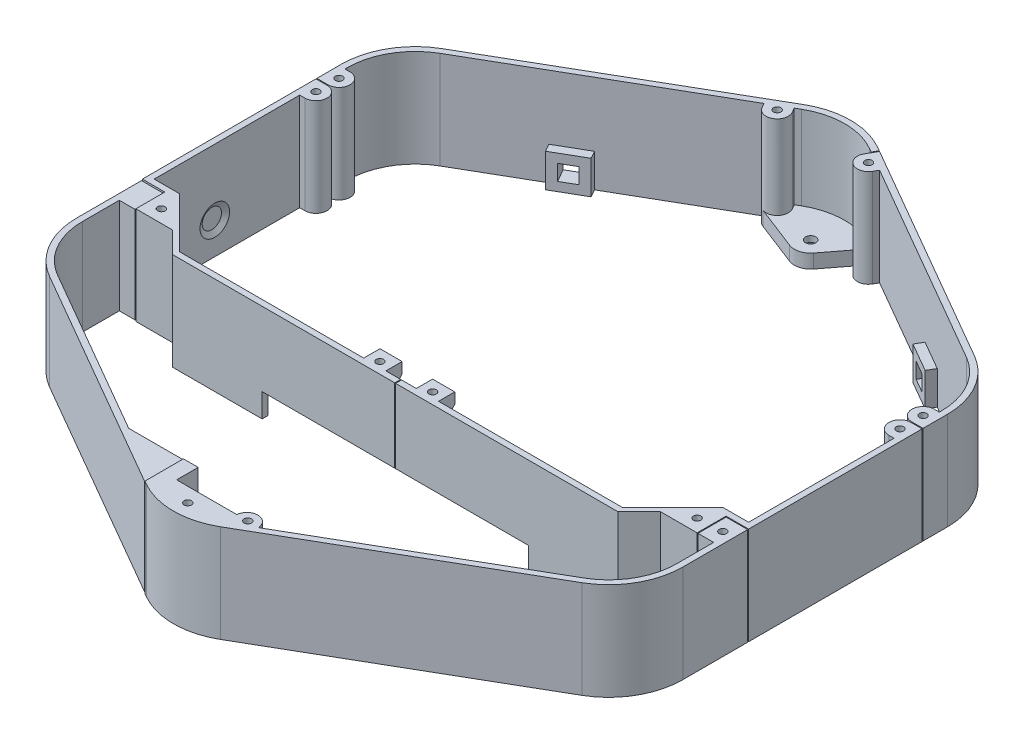
SolidWorks part; units mm, degrees
material "ABS_Perso"
ref_plane "Plan de face" through (0, 0, 0) normal (0, 0, 1) x (1, 0, 0)
ref_plane "Plan de dessus" through (0, 0, 0) normal (0, 1, 0) x (1, 0, 0)
ref_plane "Plan de droite" through (0, 0, 0) normal (1, 0, 0) x (0, 0, -1)
sketch "Esquisse1" plane through (0, 0, 0) normal (0, 1, 0) x (1, 0, 0)
  line L0 (-102.5, 0) -> (102.5, 0) construction
  line L1 (-102.5, 59.1784) -> (-102.5, -59.1784)
  line L2 (102.5, 59.1784) -> (102.5, -59.1784)
  line L3 (-102.5, -59.1784) -> (0, -118.3568)
  line L5 (0, -118.3568) -> (102.5, -59.1784)
  line L6 (102.5, 59.1784) -> (0, 118.3568)
  line L8 (0, 118.3568) -> (-102.5, 59.1784)
  line L9 (0, -118.3568) -> (0, 118.3568) construction
  line L10 (-102.5, 59.1784) -> (102.5, 59.1784) construction
  line L11 (102.5, -59.1784) -> (-102.5, -59.1784) construction
  circle A1 centre (0, 0) radius 102.5 construction
  point P13 (0, 0)
  dimension "D5" = 118.3568
  dimension "D1" = 205
  dimension "D6" = 118.3568
extrude "Boss.-Extru.1" add sketch "Esquisse1" along normal blind 33
fillet "Congé8" radius 25 6 edges at (102.5, 16.5, 59.1784) (-102.5, 16.5, 59.1784) (-102.5, 16.5, -59.1784) (102.5, 16.5, -59.1784) (0, 16.5, -118.3568) (0, 16.5, 118.3568)
sketch "Esquisse22" plane through (0, 33, 0) normal (0, 1, 0) x (1, 0, 0)
  line L0 (89, 64.6632) -> (11.5, 109.4079)
  line L1 (-11.5, 109.4079) -> (-89, 64.6632)
  line L2 (-100.5, 44.7446) -> (-100.5, -44.7446)
  line L3 (-89, -64.6632) -> (-11.5, -109.4079)
  line L4 (11.5, -109.4079) -> (89, -64.6632)
  line L5 (100.5, -44.7446) -> (100.5, 44.7446)
  line L6 (90, 66.3953) -> (12.5, 111.1399)
  line L7 (-12.5, 111.1399) -> (-90, 66.3953)
  line L8 (-102.5, 44.7446) -> (-102.5, -44.7446)
  line L9 (-90, -66.3953) -> (-12.5, -111.1399)
  line L10 (12.5, -111.1399) -> (90, -66.3953)
  line L11 (102.5, -44.7446) -> (102.5, 44.7446)
  line L12 (90, 66.3953) -> (12.5, 111.1399) construction
  line L13 (-12.5, 111.1399) -> (-90, 66.3953) construction
  line L14 (-102.5, 44.7446) -> (-102.5, -44.7446) construction
  line L15 (-90, -66.3953) -> (-12.5, -111.1399) construction
  line L16 (12.5, -111.1399) -> (90, -66.3953) construction
  line L17 (102.5, -44.7446) -> (102.5, 44.7446) construction
  arc A0 (11.5, 109.4079) -> (-11.5, 109.4079) centre (0, 89.4893) ccw
  arc A1 (-89, 64.6632) -> (-100.5, 44.7446) centre (-77.5, 44.7446) ccw
  arc A2 (-100.5, -44.7446) -> (-89, -64.6632) centre (-77.5, -44.7446) ccw
  arc A3 (-11.5, -109.4079) -> (11.5, -109.4079) centre (0, -89.4893) ccw
  arc A4 (89, -64.6632) -> (100.5, -44.7446) centre (77.5, -44.7446) ccw
  arc A5 (100.5, 44.7446) -> (89, 64.6632) centre (77.5, 44.7446) ccw
  arc A6 (12.5, 111.1399) -> (-12.5, 111.1399) centre (0, 89.4893) ccw
  arc A7 (-90, 66.3953) -> (-102.5, 44.7446) centre (-77.5, 44.7446) ccw
  arc A8 (-102.5, -44.7446) -> (-90, -66.3953) centre (-77.5, -44.7446) ccw
  arc A9 (-12.5, -111.1399) -> (12.5, -111.1399) centre (0, -89.4893) ccw
  arc A10 (90, -66.3953) -> (102.5, -44.7446) centre (77.5, -44.7446) ccw
  arc A11 (102.5, 44.7446) -> (90, 66.3953) centre (77.5, 44.7446) ccw
  arc A12 (12.5, 111.1399) -> (-12.5, 111.1399) centre (0, 89.4893) ccw construction
  arc A13 (-90, 66.3953) -> (-102.5, 44.7446) centre (-77.5, 44.7446) ccw construction
  arc A14 (-102.5, -44.7446) -> (-90, -66.3953) centre (-77.5, -44.7446) ccw construction
  arc A15 (-12.5, -111.1399) -> (12.5, -111.1399) centre (0, -89.4893) ccw construction
  arc A16 (90, -66.3953) -> (102.5, -44.7446) centre (77.5, -44.7446) ccw construction
  arc A17 (102.5, 44.7446) -> (90, 66.3953) centre (77.5, 44.7446) ccw construction
  dimension "D1" = 0
  dimension "D2" = 2
extrude "Enlèv. mat.-Extru.8" cut sketch "Esquisse22" against normal through all
sketch "Esquisse32" plane through (-100.5, 0, 0) normal (1, 0, 0) x (0, 0, -1)
  line L0 (0, 10.7) -> (0, 0) construction
  line L1 (-44.7446, 0) -> (44.7446, 0) construction
  circle A0 centre (0, 10.7) radius 5
  dimension "D2" = 10
  dimension "D1" = 10.7
extrude "Enlèv. mat.-Extru.17" cut sketch "Esquisse32" against normal blind 1
chamfer "Chanfrein1" distance 1 angle 60 1 edges at (-101.5, 10.7, -5) first distance on face at (-101.5, 10.7, -5)
mirror "Symétrie8" about plane through (0, 0, 0) normal (1, 0, 0) of "Enlèv. mat.-Extru.17"
chamfer "Chanfrein2" distance 1 angle 60 1 edges at (101.5, 10.7, -5) first distance on face at (101.5, 10.7, -5)
sketch "Esquisse33" plane through (0, 0, 0) normal (0, -1, 0) x (1, 0, 0)
  line L0 (-100.5, 20.5) -> (-80, 20.5)
  line L1 (-100.5, -44.7446) -> (-100.5, 44.7446) construction
  line L2 (-80, 20.5) -> (-80, 32.5)
  line L3 (-75, 37.5) -> (75, 37.5)
  line L4 (80, 32.5) -> (80, 20.5)
  line L5 (80, 20.5) -> (100.5, 20.5)
  line L6 (100.5, 44.7446) -> (100.5, -44.7446) construction
  line L7 (0, 0) -> (0, 37.5) construction
  line L8 (-80, 32.5) -> (-75, 37.5)
  line L9 (75, 37.5) -> (80, 32.5)
  line L10 (-100.5, 22.5) -> (-82, 22.5)
  line L11 (-82, 22.5) -> (-82, 32.8284)
  line L12 (-82, 32.8284) -> (-75.3284, 39.5)
  line L13 (-75.3284, 39.5) -> (75.3284, 39.5)
  line L14 (75.3284, 39.5) -> (82, 32.8284)
  line L15 (82, 32.8284) -> (82, 22.5)
  line L16 (82, 22.5) -> (100.5, 22.5)
  line L17 (-100.5, 22.5) -> (-100.5, 20.5)
  line L18 (100.5, 22.5) -> (100.5, 20.5)
  point P4 (-80, 37.5)
  point P5 (80, 37.5)
  dimension "D1" = 37.5
  dimension "D2" = 20.5
  dimension "D3" = 160
  dimension "D4" = 2
  dimension "D5" = 2
  dimension "D8" = 2
  dimension "D9" = 2
  dimension "D10" = 2
  dimension "D11" = 1.6464
  dimension "D12" = 1.6464
extrude "Boss.-Extru.2" add sketch "Esquisse33" against normal up to surface (33 mm away) up to face at (0, 33, 0)
sketch "Esquisse34" plane through (0, 0, 0) normal (0, -1, 0) x (1, 0, 0)
  line L3 (-82, 32.8284) -> (-82, 22.5) construction
  line L4 (-100.5, 22.5) -> (-82, 22.5)
  line L5 (-100.5, 22.5) -> (-100.5, 32.3)
  line L6 (-100.5, 32.3) -> (-82, 32.3)
  line L8 (11.5, 109.4079) -> (89, 64.6632) construction
  line L9 (-89, 64.6632) -> (-11.5, 109.4079) construction
  line L10 (11.5, 109.4079) -> (32.1436, 97.4893)
  line L11 (-32.1436, 97.4893) -> (-11.5, 109.4079)
  line L12 (-32.1436, 97.4893) -> (32.1436, 97.4893)
  line L13 (0, 112.4893) -> (0, 97.4893) construction
  line L14 (-82, 22.5) -> (-82, 32.3)
  line L16 (0, 0) -> (0, 37.5) construction
  line L17 (-75, 37.5) -> (75, 37.5) construction
  line L18 (82, 22.5) -> (82, 32.3)
  line L19 (100.5, 32.3) -> (82, 32.3)
  line L20 (100.5, 22.5) -> (100.5, 32.3)
  line L21 (100.5, 22.5) -> (82, 22.5)
  arc A0 (11.5, 109.4079) -> (-11.5, 109.4079) centre (0, 89.4893) ccw construction
  arc A1 (11.5, 109.4079) -> (-11.5, 109.4079) centre (0, 89.4893) ccw
  dimension "D2" = 15
  dimension "D1" = 9.8
extrude "Boss.-Extru.3" add sketch "Esquisse34" against normal up to surface (33 mm away) up to face at (0, 33, 48.4608)
sketch "Esquisse35" plane through (0, 0, 0) normal (0, 1, 0) x (1, 0, 0)
  line L0 (-102.5, -22.5) -> (-94.9, -22.5)
  line L1 (-102.5, 44.7446) -> (-102.5, -44.7446) construction
  line L2 (-94.9, -22.5) -> (-94.9, -32.3)
  line L3 (-32.1436, -97.4893) -> (32.1436, -97.4893) construction
  line L4 (-13.9269, -97.4893) -> (-13.6269, -97.4893)
  line L5 (-102.5, -22.5) -> (-102.5, -22.8)
  line L6 (-13.9269, -97.4893) -> (-13.9269, -110.4893)
  line L7 (-94.9, -32.3) -> (-95.2, -32.3)
  line L8 (-82, -32.3) -> (-100.5, -32.3) construction
  line L11 (-100.5, -20.5) -> (-80, -20.5) construction
  line L13 (-13.9269, -110.4893) -> (-13.6269, -110.4893)
  line L14 (-13.6269, -97.4893) -> (-13.6269, -110.4893)
  line L15 (-90, -66.3953) -> (-12.5, -111.1399) construction
  line L27 (-102.5, -22.8) -> (-95.2, -22.8)
  line L28 (-95.2, -22.8) -> (-95.2, -32.3)
  dimension "D1" = 7.3
  dimension "D2" = 13
  dimension "D3" = 2
  dimension "D4" = 0.3
  dimension "D5" = 0.3
  dimension "D6" = 0.3
extrude "Enlèv. mat.-Extru.22" cut sketch "Esquisse35" along normal through all contours L0 L2 | L14 L13 L6 L4 | L0 L2 L7 L28 L27 L5 region at (-98.7, 0, 22.624)
sketch "Esquisse36" plane through (0, 0, 0) normal (0, -1, 0) x (1, 0, 0)
  line L0 (-13.6269, 97.4893) -> (32.1436, 97.4893) construction
  line L1 (-8.6269, 97.4893) -> (8.6269, 97.4893)
  line L2 (-8.6269, 97.4893) -> (-8.6269, 104.7893)
  line L3 (-8.6269, 104.7893) -> (8.6269, 104.7893)
  line L4 (8.6269, 97.4893) -> (8.6269, 104.7893)
  line L6 (0, 97.4893) -> (0, 0) construction
  line L7 (-13.6269, 97.4893) -> (-13.6269, 110.4893) construction
  dimension "D1" = 5
  dimension "D2" = 7.3
extrude "Enlèv. mat.-Extru.23" cut sketch "Esquisse36" against normal through all
sketch "Esquisse37" plane through (-95.2, 0, 0) normal (-1, 0, 0) x (0, 0, 1)
  line L0 (22.8, 16.5) -> (24.8, 16.5) construction
  line L1 (24.8, 19.25) -> (30.3, 19.25)
  line L2 (24.8, 19.25) -> (24.8, 13.75)
  line L3 (24.8, 13.75) -> (30.3, 13.75)
  line L4 (30.3, 19.25) -> (30.3, 13.75)
  line L5 (22.8, 33) -> (22.8, 0) construction
  line L6 (30.3, 16.5) -> (32.3, 16.5) construction
  line L7 (32.3, 33) -> (32.3, 0) construction
  dimension "D1" = 5.5
extrude "Enlèv. mat.-Extru.24" cut sketch "Esquisse37" against normal up to surface (15.2 mm away) and the other way blind 5.3 up to face at (-80, 16.5, 26.5)
sketch "Esquisse38" plane through (-13.9269, 0, 0) normal (1, 0, 0) x (0, 0, -1)
  line L0 (-99.2893, 16.5) -> (-97.4893, 16.5) construction
  line L1 (-104.7893, 19.25) -> (-99.2893, 19.25)
  line L2 (-104.7893, 19.25) -> (-104.7893, 13.75)
  line L3 (-104.7893, 13.75) -> (-99.2893, 13.75)
  line L4 (-99.2893, 19.25) -> (-99.2893, 13.75)
  line L5 (-97.4893, 33) -> (-97.4893, 0) construction
  line L6 (-104.7893, 33) -> (-104.7893, 0) construction
  dimension "D1" = 5.5
extrude "Enlèv. mat.-Extru.25" cut sketch "Esquisse38" along normal up to surface (5.3 mm away) and the other way blind 5.3 up to face at (-8.6269, 16.5, 101.1393)
sketch "Esquisse39" plane through (0, 0, 0) normal (1, 0, 0) x (0, 0, -1)
  line L0 (-111.1399, 33) -> (-114.4893, 33) construction
  line L1 (-114.4893, 33) -> (114.4893, 33)
  line L2 (-114.4893, 33) -> (-114.4893, 32.7)
  line L3 (-114.4893, 32.7) -> (114.4893, 32.7)
  line L4 (114.4893, 33) -> (114.4893, 32.7)
  line L5 (114.4893, 0) -> (114.4893, 33) construction
  line L6 (111.1399, 0) -> (114.4893, 0) construction
  line L7 (114.4893, 0) -> (-114.4893, 0)
  line L8 (114.4893, 0) -> (114.4893, 0.3)
  line L9 (114.4893, 0.3) -> (-114.4893, 0.3)
  line L10 (-114.4893, 0) -> (-114.4893, 0.3)
  dimension "D1" = 0.3
extrude "Enlèv. mat.-Extru.26" cut sketch "Esquisse39" against normal through all
sketch "Esquisse40" plane through (0, 33, 0) normal (0, 1, 0) x (1, 0, 0)
  line L0 (32.1436, -97.4893) -> (19.4996, -104.7893)
  line L1 (19.4996, -104.7893) -> (8.6269, -104.7893)
  line L2 (8.6269, -104.7893) -> (8.6269, -97.4893)
  line L3 (8.6269, -97.4893) -> (32.1436, -97.4893)
  line L4 (32.1436, -97.4893) -> (89, -64.6632) construction
extrude "Enlèv. mat.-Extru.27" cut sketch "Esquisse40" against normal through all
sketch "Esquisse41" plane through (0, 33, 0) normal (0, 1, 0) x (1, 0, 0)
  line L0 (-82, -32.8284) -> (-82.5284, -32.3)
  line L1 (-82, -32.3) -> (-94.9, -32.3) construction
  line L2 (-82.5284, -32.3) -> (-82, -32.3)
  line L3 (-82, -32.3) -> (-82, -32.8284)
  line L4 (-75.3284, -39.5) -> (-82, -32.8284) construction
  line L5 (0, 0) -> (0, -39.5) construction
  line L6 (75.3284, -39.5) -> (-75.3284, -39.5) construction
  line L7 (82, -32.3) -> (82, -32.8284)
  line L8 (82.5284, -32.3) -> (82, -32.3)
  line L9 (82, -32.8284) -> (82.5284, -32.3)
extrude "Boss.-Extru.4" add sketch "Esquisse41" against normal up to surface (33 mm away) up to face at (0, 0, -15.8425)
sketch "Esquisse42" plane through (0, 33, 0) normal (0, 1, 0) x (1, 0, 0)
  line L0 (-80, -32.5) -> (-92, -20.5)
  line L1 (-100.5, -20.5) -> (-80, -20.5) construction
  line L2 (-92, -20.5) -> (-80, -20.5)
  line L3 (-80, -20.5) -> (-80, -32.5)
  line L4 (-80, -32.5) -> (-75, -37.5) construction
  line L5 (0, 0) -> (0, -39.5) construction
  line L6 (75.3284, -39.5) -> (-75.3284, -39.5) construction
  line L7 (80, -20.5) -> (80, -32.5)
  line L8 (92, -20.5) -> (80, -20.5)
  line L9 (80, -32.5) -> (92, -20.5)
extrude "Enlèv. mat.-Extru.28" cut sketch "Esquisse42" against normal through all
sketch "Esquisse43" plane through (0, 0, 0) normal (0, -1, 0) x (-1, 0, 0)
  line L0 (0, 0) -> (0, 101) construction
  line L1 (-19.4996, -104.7893) -> (8.6269, -104.7893) construction
  line L2 (8.6269, -104.7893) -> (8.6269, -97.4893) construction
  line L3 (-8.6886, -104.7893) -> (8.6269, -104.7893)
  line L4 (8.6269, -104.7893) -> (8.6269, -97.4893)
  line L5 (0, 0) -> (102.5, 0) construction
  line L6 (102.5, 44.7446) -> (102.5, -22.5) construction
  line L7 (8.6269, -97.4893) -> (1.3352, -95.6645)
  line L8 (-4.7159, -98.1697) -> (-8.6886, -104.7893)
  line L9 (-4.3634, 97.6518) -> (-12.8057, 108.654)
  line L10 (4.3634, 97.6518) -> (12.8057, 108.654)
  line L11 (-89, 64.6632) -> (-11.5, 109.4079) construction
  line L12 (11.5, 109.4079) -> (89, 64.6632) construction
  line L13 (11.5, 109.4079) -> (12.8057, 108.654)
  line L14 (-12.8057, 108.654) -> (-11.5, 109.4079)
  line L15 (-12.8057, 108.654) -> (12.8057, 108.654) construction
  line L16 (0, 101) -> (0, 108.654) construction
  arc A0 (-4.7159, -98.1697) -> (1.3352, -95.6645) centre (0, -101) cw
  arc A1 (-4.3634, 97.6518) -> (4.3634, 97.6518) centre (0, 101) ccw
  arc A3 (11.5, 109.4079) -> (-11.5, 109.4079) centre (0, 89.4893) ccw construction
  arc A4 (11.5, 109.4079) -> (-11.5, 109.4079) centre (0, 89.4893) ccw
  dimension "D2" = 75
  dimension "D3" = 11
  dimension "D1" = 101
extrude "Boss.-Extru.5" add sketch "Esquisse43" against normal blind 4.7 contours A0 L3 | A1 region at (-1.0275, 0, 100.7659) region at (0, 0, -105.2161)
sketch "Esquisse44" plane through (0, 0, 0) normal (0, -1, 0) x (1, 0, 0)
  line L0 (0, 0) -> (-102.5, 0) construction
  line L1 (-1.6743, -103.9) -> (1.6743, -103.9)
  line L2 (1.6743, -103.9) -> (3.3486, -101)
  line L3 (3.3486, -101) -> (1.6743, -98.1)
  line L4 (1.6743, -98.1) -> (-1.6743, -98.1)
  line L5 (-1.6743, -98.1) -> (-3.3486, -101)
  line L6 (-3.3486, -101) -> (-1.6743, -103.9)
  line L7 (-102.5, -44.7446) -> (-102.5, 22.5) construction
  line L8 (-3.3486, 101) -> (-1.6743, 103.9)
  line L9 (-1.6743, 98.1) -> (-3.3486, 101)
  line L10 (1.6743, 98.1) -> (-1.6743, 98.1)
  line L11 (3.3486, 101) -> (1.6743, 98.1)
  line L12 (1.6743, 103.9) -> (3.3486, 101)
  line L13 (-1.6743, 103.9) -> (1.6743, 103.9)
  circle A0 centre (0, -101) radius 2.9 construction
  circle A1 centre (0, 101) radius 2.9 construction
  dimension "D1" = 5.8
extrude "Enlèv. mat.-Extru.29" cut sketch "Esquisse44" against normal blind 2.7
sketch "Esquisse45" plane through (0, 2.7, 0) normal (0, -1, 0) x (1, 0, 0)
  line L0 (0, 0) -> (-102.5, 0) construction
  line L1 (-102.5, -44.7446) -> (-102.5, 22.5) construction
  circle A0 centre (0, -101) radius 1.75
  circle A1 centre (0, 101) radius 1.75
  dimension "D1" = 3.5
extrude "Enlèv. mat.-Extru.30" cut sketch "Esquisse45" against normal through all
fillet "Congé10" radius 8 2 edges at (8.6886, 2.35, 104.7893) (-8.6269, 2.35, 97.4893)
sketch "Esquisse46" plane through (0, 0, 37.5) normal (0, 0, -1) x (-1, 0, 0)
  line L0 (75, 0) -> (-75, 0) construction
  line L1 (-45, 0) -> (45, 0)
  line L2 (-45, 0) -> (-45, 8)
  line L3 (-45, 8) -> (45, 8)
  line L4 (45, 0) -> (45, 8)
  dimension "D1" = 8
  dimension "D2" = 90
extrude "Enlèv. mat.-Extru.31" cut sketch "Esquisse46" against normal up to next (2 mm away)
sketch "Esquisse47" plane through (0, 33, 0) normal (0, 1, 0) x (1, 0, 0)
  line L0 (12.8057, 108.654) -> (13.8057, 110.3861)
  line L1 (13.8057, 110.3861) -> (14.0655, 110.2361)
  line L2 (90, 66.3953) -> (12.5, 111.1399) construction
  line L3 (14.0655, 110.2361) -> (13.0655, 108.504)
  line L4 (89, 64.6632) -> (11.5, 109.4079) construction
  line L5 (13.0655, 108.504) -> (12.8057, 108.654)
  line L6 (-75, -37.5) -> (75, -37.5) construction
  line L7 (-0.15, -37.5) -> (0.15, -37.5)
  line L8 (-0.15, -37.5) -> (-0.15, -39.5)
  line L9 (-0.15, -39.5) -> (0.15, -39.5)
  line L10 (0.15, -37.5) -> (0.15, -39.5)
  line L11 (75.3284, -39.5) -> (-75.3284, -39.5) construction
  line L12 (0, 0) -> (0, -37.5) construction
  line L13 (-102.5, 44.7446) -> (-102.5, -22.5) construction
  line L14 (-102.5, 36.5) -> (102.5, 36.5)
  line L15 (-102.5, 36.5) -> (-102.5, 36.2)
  line L16 (-102.5, 36.2) -> (102.5, 36.2)
  line L17 (102.5, 36.5) -> (102.5, 36.2)
  line L18 (102.5, -44.7446) -> (102.5, 44.7446) construction
  line L19 (89, 64.6632) -> (12.8057, 108.654) construction
  dimension "D1" = 0.3
  dimension "D2" = 0.3
  dimension "D3" = 36.2
  dimension "D4" = 0.3
extrude "Enlèv. mat.-Extru.32" cut sketch "Esquisse47" against normal through all
sketch "Esquisse48" plane through (0, 33, 0) normal (0, 1, 0) x (1, 0, 0)
  line L0 (94.9, -32.3) -> (94.9, -22.5)
  line L1 (100.5, -32.3) -> (82.5284, -32.3) construction
  line L2 (94.9, -22.5) -> (102.5, -22.5)
  line L3 (102.5, -44.7446) -> (102.5, 36.2) construction
  line L4 (-102.5, -22.5) -> (-94.9, -22.5) construction
  line L5 (-94.9, -22.5) -> (-94.9, -32.3) construction
  line L6 (95.2, -32.3) -> (95.2, -22.8)
  line L7 (95.2, -22.8) -> (102.5, -22.8)
  line L8 (95.2, -32.3) -> (94.9, -32.3)
  line L9 (102.5, -22.5) -> (102.5, -22.8)
  dimension "D1" = 0.3
extrude "Enlèv. mat.-Extru.33" cut sketch "Esquisse48" against normal through all
sketch "Esquisse49" plane through (0, 33, 0) normal (0, 1, 0) x (1, 0, 0)
  line L1 (12.5, -111.1399) -> (90, -66.3953) construction
  line L2 (100.5, 36.5) -> (98.75, 36.5)
  line L3 (90, 66.3953) -> (14.0655, 110.2361) construction
  line L4 (19.5607, 104.754) -> (18.6857, 103.2385)
  line L5 (13.0655, 108.504) -> (12.1905, 106.9885)
  line L6 (13.0655, 108.504) -> (14.0655, 110.2361) construction
  line L7 (89, 64.6632) -> (13.0655, 108.504) construction
  line L8 (19.5607, 104.754) -> (13.0655, 108.504)
  line L9 (98.75, 44) -> (100.5, 44)
  line L10 (100.5, 36.5) -> (100.5, 44.7446) construction
  line L11 (100.5, 44) -> (100.5, 36.5)
  line L12 (102.5, 36.5) -> (102.5, 44.7446) construction
  line L13 (100.5, 36.2) -> (98.75, 36.2)
  line L14 (98.75, 28.7) -> (100.5, 28.7)
  line L15 (100.5, -20.5) -> (100.5, 36.2) construction
  line L16 (100.5, 28.7) -> (100.5, 36.2)
  line L17 (102.5, -22.5) -> (102.5, 36.2) construction
  line L18 (0, 0) -> (0, -38.0003) construction
  line L19 (-100.5, 28.7) -> (-100.5, 36.2)
  line L20 (-98.75, 28.7) -> (-100.5, 28.7)
  line L21 (-100.5, 36.2) -> (-98.75, 36.2)
  line L22 (-100.5, 44) -> (-100.5, 36.5)
  line L23 (-98.75, 44) -> (-100.5, 44)
  line L24 (-100.5, 36.5) -> (-98.75, 36.5)
  line L25 (-19.5607, 104.754) -> (-13.0655, 108.504)
  line L26 (-13.0655, 108.504) -> (-12.1905, 106.9885)
  line L27 (-19.5607, 104.754) -> (-18.6857, 103.2385)
  line L28 (15.4381, 105.1135) -> (15.4381, -105.1135) construction
  circle A0 centre (15.4381, 105.1135) radius 1.25
  arc A1 (12.1905, 106.9885) -> (18.6857, 103.2385) centre (15.4381, 105.1135) ccw
  arc A2 (98.75, 36.5) -> (98.75, 44) centre (98.75, 40.25) cw
  circle A3 centre (98.75, 40.25) radius 1.25
  arc A4 (98.75, 36.2) -> (98.75, 28.7) centre (98.75, 32.45) ccw
  circle A5 centre (98.75, 32.45) radius 1.25
  circle A6 centre (-98.75, 32.45) radius 1.25
  arc A7 (-98.75, 36.2) -> (-98.75, 28.7) centre (-98.75, 32.45) cw
  circle A8 centre (-98.75, 40.25) radius 1.25
  arc A9 (-98.75, 36.5) -> (-98.75, 44) centre (-98.75, 40.25) ccw
  arc A10 (-12.1905, 106.9885) -> (-18.6857, 103.2385) centre (-15.4381, 105.1135) cw
  circle A11 centre (-15.4381, 105.1135) radius 1.25
  circle A12 centre (15.4381, -105.1135) radius 3.75
  dimension "D1" = 3.75
  dimension "D2" = 2.5
extrude "Boss.-Extru.6" add sketch "Esquisse49" against normal up to surface (33 mm away) up to face at (0, 0, -101)
sketch "Esquisse50" plane through (0, 4.7, 0) normal (0, 1, 0) x (1, 0, 0)
  line L0 (-12.1905, 106.9885) -> (-13.0655, 108.504) construction
  line L1 (-11.5, 109.4079) -> (-13.0655, 108.504) construction
  line L3 (-12.1905, 106.9885) -> (-13.0655, 108.504)
  line L4 (-12.8057, 108.654) -> (-13.0655, 108.504)
  line L5 (-4.3634, 97.6518) -> (-12.8057, 108.654)
  line L6 (-16.7947, 101.6174) -> (-1.9897, 95.8725)
  line L7 (-4.3634, 97.6518) -> (-12.8057, 108.654) construction
  line L8 (-11.5, 109.4079) -> (-12.8057, 108.654) construction
  arc A0 (-18.6857, 103.2385) -> (-12.1905, 106.9885) centre (-15.4381, 105.1135) ccw construction
  arc A1 (-4.3634, 97.6518) -> (4.3634, 97.6518) centre (0, 101) ccw construction
  arc A2 (-16.7947, 101.6174) -> (-12.1905, 106.9885) centre (-15.4381, 105.1135) ccw
  arc A3 (-4.3634, 97.6518) -> (-1.9897, 95.8725) centre (0, 101) ccw
extrude "Boss.-Extru.7" add sketch "Esquisse50" against normal up to surface (4.7 mm away) up to face at (0, 0, -101)
sketch "Esquisse51" plane through (0, 33, 0) normal (0, 1, 0) x (1, 0, 0)
  line L0 (0, -114.4893) -> (0, -104.7893) construction
  line L1 (-8.6269, -104.7893) -> (11.7022, -104.7893) construction
  line L2 (95.2, -27.55) -> (102.5, -27.55) construction
  line L3 (95.2, -32.3) -> (95.2, -22.8) construction
  line L4 (102.5, -44.7446) -> (102.5, -22.8) construction
  line L5 (90.5945, -27.9945) -> (87.55, -24.95) construction
  line L6 (75, -37.5) -> (92, -20.5) construction
  line L7 (90.5945, -27.9945) -> (90.5945, -32.3) construction
  line L8 (94.9, -32.3) -> (82.5284, -32.3) construction
  line L9 (90.5945, -27.9945) -> (94.9, -27.9945) construction
  line L10 (94.9, -22.5) -> (94.9, -32.3) construction
  line L11 (0, 0) -> (0, -28.1409) construction
  line L12 (-90.5945, -27.9945) -> (-94.9, -27.9945) construction
  line L13 (-90.5945, -27.9945) -> (-90.5945, -32.3) construction
  line L14 (-90.5945, -27.9945) -> (-87.55, -24.95) construction
  line L15 (11.7022, -104.7893) -> (-8.6269, -104.7893) construction
  line L16 (15.4381, 105.1135) -> (15.4381, -104.7893) construction
  circle A1 centre (15.4381, -104.7893) radius 1.25
  circle A2 centre (98.85, -27.55) radius 1.25
  circle A4 centre (90.5945, -27.9945) radius 1.25
  circle A5 centre (-90.5945, -27.9945) radius 1.25
  arc A6 (-12.5, -111.1399) -> (12.5, -111.1399) centre (0, -89.4893) ccw construction
  circle A7 centre (0, -109.6393) radius 1.25
  dimension "D1" = 2.5
extrude "Enlèv. mat.-Extru.34" cut sketch "Esquisse51" against normal through all
sketch "Esquisse52" plane through (0, 33, 0) normal (0, 1, 0) x (1, 0, 0)
  line L0 (75.3284, -39.5) -> (0.15, -39.5) construction
  line L1 (-5.15, -39.5) -> (-12.65, -39.5)
  line L2 (-5.15, -39.5) -> (-5.15, -32)
  line L3 (-5.15, -32) -> (-12.65, -32)
  line L4 (-12.65, -39.5) -> (-12.65, -32)
  line L5 (5.15, -39.5) -> (12.65, -39.5)
  line L6 (5.15, -39.5) -> (5.15, -32)
  line L7 (5.15, -32) -> (12.65, -32)
  line L8 (12.65, -39.5) -> (12.65, -32)
  line L9 (-0.15, -39.5) -> (-75.3284, -39.5) construction
  line L10 (-5.15, -39.5) -> (-0.15, -39.5) construction
  line L13 (0.15, -39.5) -> (5.15, -39.5) construction
  dimension "D1" = 7.5
  dimension "D2" = 7.5
  dimension "D3" = 5
extrude "Boss.-Extru.8" add sketch "Esquisse52" against normal up to surface (25 mm away) up to face at (-22.575, 8, 38.5)
sketch "Esquisse53" plane through (0, 33, 0) normal (0, 1, 0) x (1, 0, 0)
  line L0 (-8.9, -32) -> (-8.9, -39.5) construction
  line L1 (-5.15, -32) -> (-12.65, -32) construction
  line L2 (-0.15, -39.5) -> (-75.3284, -39.5) construction
  line L3 (8.9, -32) -> (8.9, -39.5) construction
  line L4 (12.65, -32) -> (5.15, -32) construction
  line L5 (75.3284, -39.5) -> (0.15, -39.5) construction
  circle A0 centre (-8.9, -35.75) radius 1.25
  circle A1 centre (8.9, -35.75) radius 1.25
  dimension "D1" = 2.5
extrude "Enlèv. mat.-Extru.35" cut sketch "Esquisse53" against normal through all
sketch "Esquisse54" plane through (-12.65, 0, 0) normal (-1, 0, 0) x (0, 0, 1)
  line L0 (37.5, 33) -> (37.5, 0) construction
  line L1 (39.5, 33) -> (32.3, 33) construction
  line L2 (34.6803, 25.7605) -> (37.5, 19.9792)
  line L3 (37.5, 19.9792) -> (37.5, 0)
  line L4 (-36.2, 0) -> (22.5, 0) construction
  line L5 (11.8948, 0) -> (11.8948, 20.5)
  line L6 (37.5, 0) -> (11.8948, 0)
  arc A2 (34.6803, 25.7605) -> (11.8948, 20.5) centre (23.8948, 20.5) ccw
  dimension "D1" = 12
  dimension "D2" = 13.6052
  dimension "D3" = 12.5
  dimension "D4" = 26
extrude "Enlèv. mat.-Extru.36" cut sketch "Esquisse54" against normal up to surface (25.3 mm away) up to face at (12.65, 20.5, 34.75)
sketch "Esquisse55" plane through (0, 0, 0) normal (0, -1, 0) x (1, 0, 0)
  line L0 (1.9897, 95.8725) -> (16.7947, 101.6174)
  line L1 (4.7159, 98.1697) -> (6.3581, 100.906) construction
  line L2 (4.7159, 98.1697) -> (6.3581, 100.906)
  arc A0 (-1.3352, 95.6645) -> (4.7159, 98.1697) centre (0, 101) ccw construction
  arc A1 (11.7172, 104.6473) -> (19.1741, 104.7893) centre (15.4381, 105.1135) ccw construction
  arc A2 (11.7172, 104.6473) -> (6.3581, 100.906) centre (13.2176, 96.7893) ccw construction
  arc A3 (11.7172, 104.6473) -> (16.7947, 101.6174) centre (15.4381, 105.1135) ccw
  arc A4 (11.7172, 104.6473) -> (6.3581, 100.906) centre (13.2176, 96.7893) ccw
  arc A5 (1.9897, 95.8725) -> (4.7159, 98.1697) centre (0, 101) ccw
extrude "Boss.-Extru.9" add sketch "Esquisse55" against normal up to surface (4.7 mm away) up to face at (0, 4.7, 99.25)
sketch "Esquisse56" plane through (-51.25, 0, -88.7676) normal (-0.5, 0, -0.866) x (-0.866, 0, 0.5)
  line L0 (-44.7446, 0) -> (44.7446, 0) construction
  line L1 (14.8232, 3) -> (9.5232, 3)
  line L2 (14.8232, 3) -> (14.8232, 8.3)
  line L3 (14.8232, 8.3) -> (9.5232, 8.3)
  line L4 (9.5232, 3) -> (9.5232, 8.3)
  line L5 (12.1732, 8.3) -> (12.1732, 3) construction
  dimension "D1" = 5.3
  dimension "D2" = 9.5232
  dimension "D3" = 3
extrude "Enlèv. mat.-Extru.37" cut sketch "Esquisse56" against normal blind 13
sketch "Esquisse57" plane through (-50.25, 0, -87.0356) normal (0.5, 0, 0.866) x (0.866, 0, -0.5)
  line L0 (-9.5232, 8.3) -> (-14.8232, 8.3) construction
  line L1 (-14.8232, 8.3) -> (-14.8232, 3) construction
  line L2 (-14.8232, 3) -> (-9.5232, 3) construction
  line L3 (-9.5232, 3) -> (-9.5232, 8.3) construction
  line L4 (-9.5232, 8.3) -> (-14.8232, 8.3)
  line L5 (-14.8232, 8.3) -> (-14.8232, 3)
  line L6 (-14.8232, 3) -> (-9.5232, 3)
  line L7 (-9.5232, 3) -> (-9.5232, 8.3)
  line L8 (-6.5232, 11.3) -> (-17.8232, 11.3)
  line L9 (-17.8232, 11.3) -> (-17.8232, 0)
  line L10 (-17.8232, 0) -> (-6.5232, 0)
  line L11 (-6.5232, 0) -> (-6.5232, 11.3)
  dimension "D1" = 3
extrude "Boss.-Extru.10" add sketch "Esquisse57" along normal blind 3
sketch "Esquisse58" plane through (51.25, 0, -88.7676) normal (0.5, 0, -0.866) x (-0.866, 0, -0.5)
  line L0 (-12.1732, 8.3) -> (-12.1732, 3) construction
  line L1 (-14.8232, 8.3) -> (-9.5232, 8.3)
  line L2 (-14.8232, 8.3) -> (-14.8232, 3)
  line L3 (-14.8232, 3) -> (-9.5232, 3)
  line L4 (-9.5232, 8.3) -> (-9.5232, 3)
  line L5 (-44.7446, 0) -> (35.4369, 0) construction
  dimension "D1" = 5.3
  dimension "D2" = 9.5232
  dimension "D3" = 3
extrude "Enlèv. mat.-Extru.38" cut sketch "Esquisse58" against normal up to next (2 mm away)
sketch "Esquisse59" plane through (50.25, 0, -87.0356) normal (-0.5, 0, 0.866) x (0.866, 0, 0.5)
  line L0 (9.5232, 3) -> (14.8232, 3) construction
  line L1 (14.8232, 3) -> (14.8232, 8.3) construction
  line L2 (14.8232, 8.3) -> (9.5232, 8.3) construction
  line L3 (9.5232, 8.3) -> (9.5232, 3) construction
  line L4 (9.5232, 3) -> (14.8232, 3)
  line L5 (14.8232, 3) -> (14.8232, 8.3)
  line L6 (14.8232, 8.3) -> (9.5232, 8.3)
  line L7 (9.5232, 8.3) -> (9.5232, 3)
  line L8 (17.8232, 0) -> (17.8232, 11.3)
  line L9 (17.8232, 11.3) -> (6.5232, 11.3)
  line L10 (6.5232, 11.3) -> (6.5232, 0)
  line L11 (6.5232, 0) -> (17.8232, 0)
  dimension "D1" = 3
extrude "Boss.-Extru.11" add sketch "Esquisse59" along normal blind 3
